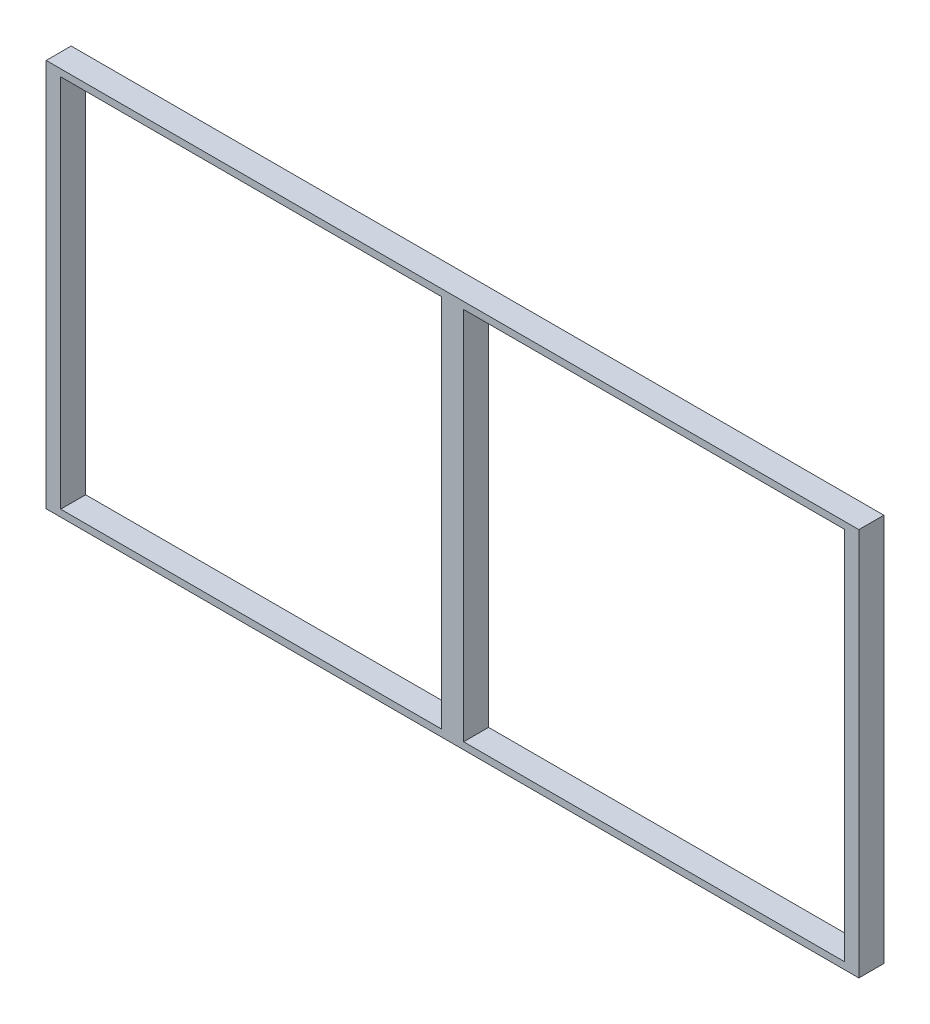
SolidWorks part; units mm, degrees
ref_plane "Спереди" through (0, 0, 0) normal (0, 0, 1) x (1, 0, 0)
ref_plane "Сверху" through (0, 0, 0) normal (0, 1, 0) x (1, 0, 0)
ref_plane "Справа" through (0, 0, 0) normal (1, 0, 0) x (0, 0, -1)
sketch "Эскиз1" plane through (0, 0, 0) normal (0, 0, 1) x (1, 0, 0)
  line L1 (-2930, 1400) -> (2930, 1400)
  line L2 (-2930, 1400) -> (-2930, -1400)
  line L3 (-2930, -1400) -> (2930, -1400)
  line L4 (2930, 1400) -> (2930, -1400)
  line L5 (-2930, 1400) -> (2930, -1400) construction
  line L6 (-2930, -1400) -> (2930, 1400) construction
  line L7 (-2825.3571, 1350) -> (-80, 1350)
  line L8 (-2825.3571, 1350) -> (-2825.3571, -1350)
  line L9 (-2825.3571, -1350) -> (-80, -1350)
  line L10 (-80, 1350) -> (-80, -1350)
  line L11 (80, 1350) -> (2825.3571, 1350)
  line L12 (80, 1350) -> (80, -1350)
  line L13 (80, -1350) -> (2825.3571, -1350)
  line L14 (2825.3571, 1350) -> (2825.3571, -1350)
  point P0 (0, 0)
  point P14 (0, 0)
  point P15 (-2728.2546, -1216.0825)
  point P16 (-2804.3919, 1339.9825)
  point P17 (-2817.0815, -1346.0458)
  point P18 (0, 0)
  point P19 (2821.3114, -1348.0669)
  point P20 (2829.7711, 1352.109)
  point P21 (0, 0)
  point P22 (0, 0)
extrude "Бобышка-Вытянуть1" add sketch "Эскиз1" along normal blind 180
